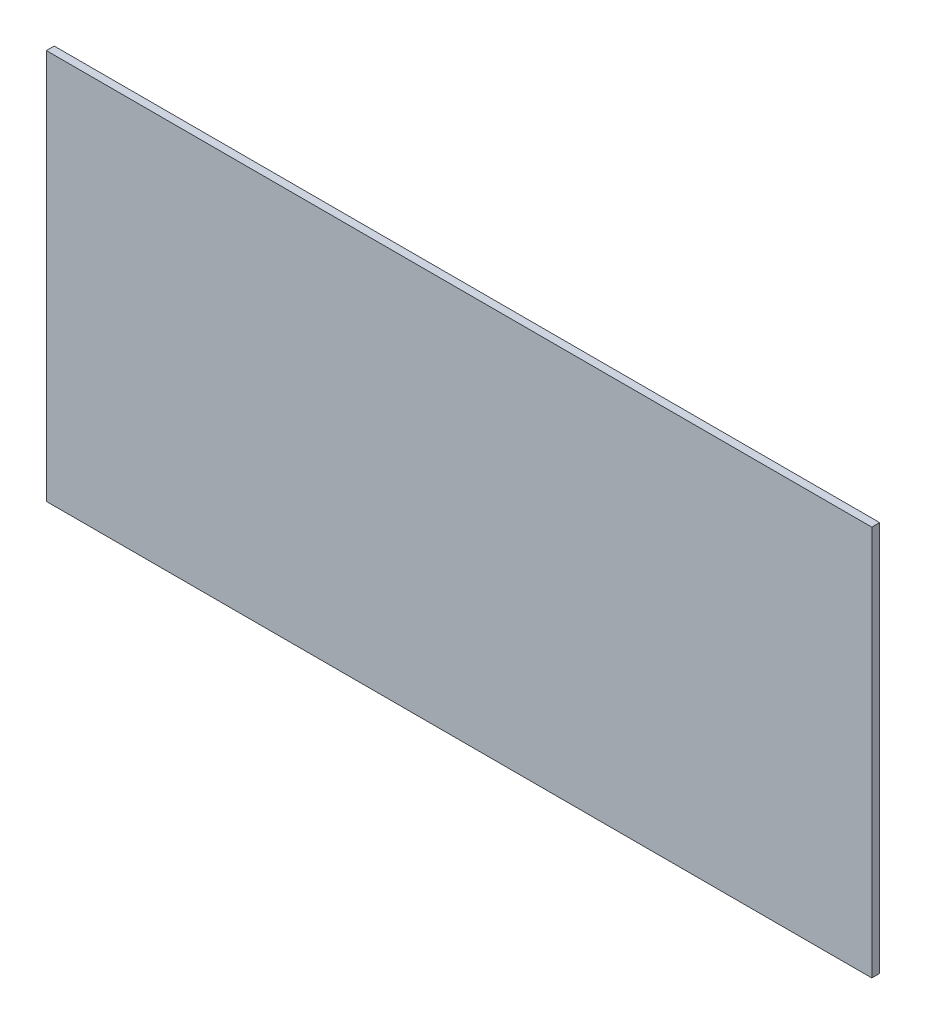
SolidWorks part; units mm, degrees
ref_plane "Ön Düzlem" through (0, 0, 0) normal (0, 0, 1) x (1, 0, 0)
ref_plane "Üst Düzlem" through (0, 0, 0) normal (0, 1, 0) x (1, 0, 0)
ref_plane "Sağ Düzlem" through (0, 0, 0) normal (1, 0, 0) x (0, 0, -1)
sketch "Çizim1" plane through (0, 0, 0) normal (0, 0, 1) x (1, 0, 0)
  line L1 (0, 0) -> (630, 0)
  line L2 (0, 0) -> (0, -298)
  line L3 (0, -298) -> (630, -298)
  line L4 (630, 0) -> (630, -298)
  dimension "D1" = 630
  dimension "D2" = 298
base flange "Taban-Flanş1" sketch "Çizim1" thickness 6 reverse thickness direction no parameters "D1"=12
sketch "Büküm-Çizgileri1" [suppressed] plane through (0, 0, 0) normal (0, 1, 0) x (1, 0, 0)
sketch "Sınırlandırma-Kutusu1" [suppressed] plane through (0, 0, 0) normal (0, 1, 0) x (1, 0, 0)
sheet metal parameters "Sac-Levha1" thickness 6 parameters "D1"=12
flat pattern "Düz-Çoğaltma1" [suppressed]
sketch "Büküm-Çizgileri2" plane through (0, 0, 0) normal (0, 1, 0) x (1, 0, 0)
sketch3d "Sınırlandırma-Kutusu2" [suppressed]
  line L0 (0, -298, 0) -> (630, -298, 0) construction
  line L1 (0, 0, 0) -> (630, 0, 0) construction
  line L2 (0, -298, 0) -> (0, 0, 0) construction
  line L3 (630, -298, 0) -> (630, 0, 0) construction
